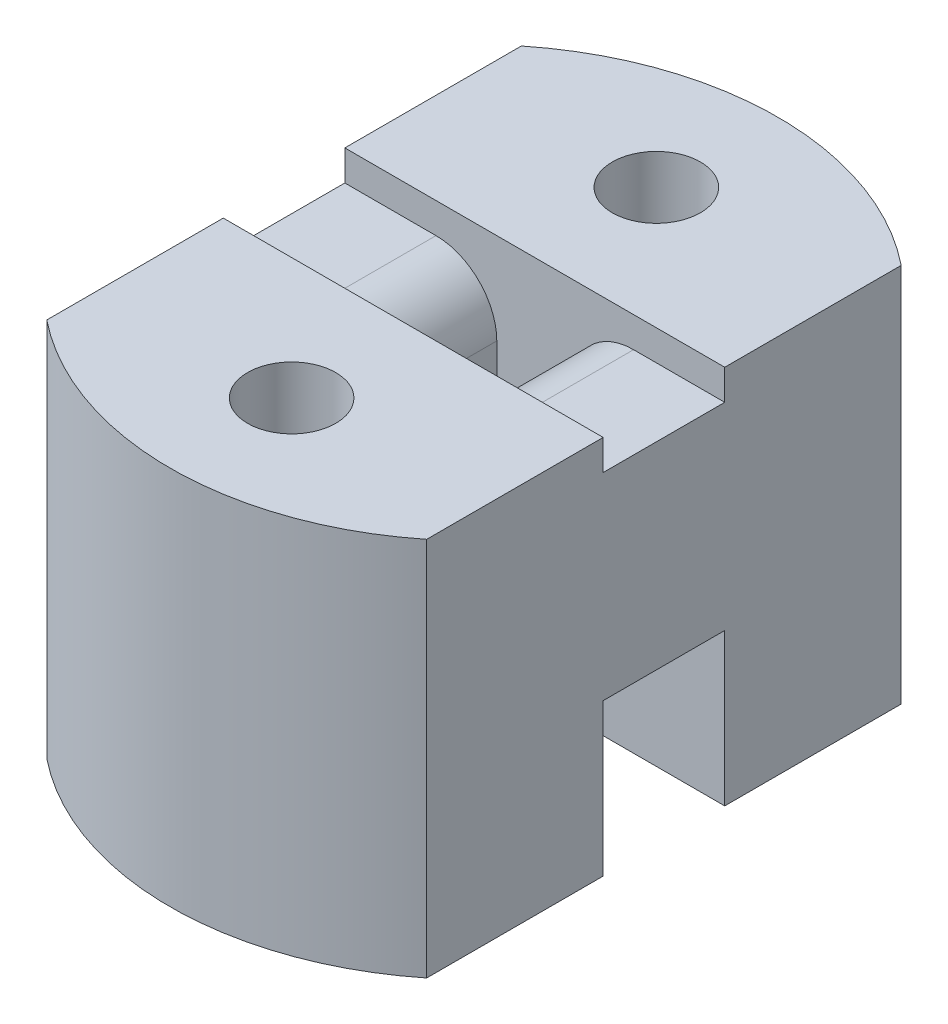
SolidWorks part; units mm, degrees
ref_plane "Front Plane" through (0, 0, 0) normal (0, 0, 1) x (1, 0, 0)
ref_plane "Top Plane" through (0, 0, 0) normal (0, 1, 0) x (1, 0, 0)
ref_plane "Right Plane" through (0, 0, 0) normal (1, 0, 0) x (0, 0, -1)
sketch "Sketch1" plane through (0, 0, 0) normal (0, 1, 0) x (1, 0, 0)
  circle A0 centre (0, 0) radius 20
  dimension "D1" = 40
extrude "Boss-Extrude1" add sketch "Sketch1" along normal blind 25
sketch "Sketch2" plane through (0, 25, 0) normal (0, 1, 0) x (1, 0, 0)
  line L0 (20, 0) -> (0, 0) construction
  line L1 (-20, 4) -> (20, 4)
  line L2 (-20, 4) -> (-20, -4)
  line L3 (-20, -4) -> (20, -4)
  line L4 (20, 4) -> (20, -4)
  circle A0 centre (0, 0) radius 20 construction
  dimension "D1" = 8
extrude "Cut-Extrude1" cut sketch "Sketch2" against normal blind 2
sketch "Sketch3" plane through (0, 25, 0) normal (0, 1, 0) x (1, 0, 0)
  line L0 (0, 0) -> (0, 12) construction
  line L3 (0, 0) -> (0, -12) construction
  dimension "D1" = 12
hole_wizard "M5 Clearance Hole1" positions "3DSketch1" profile "Sketch4" hole size "M5" standard "ANSI Metric" end condition through all
sketch3d "3DSketch1"
  point P0 (0, 25, -12)
  point P3 (0, 25, 12)
sketch "Sketch4" plane through (0, 25, -12) normal (1, 0, 0) x (0, 0, 1)
  line L0 (0, 0) -> (0, 25)
  line L1 (0, 25) -> (2.9, 25)
  line L2 (2.9, 25) -> (2.9, 0)
  line L5 (2.9, 0) -> (0, 0)
  line L11 (0, -6.35) -> (0, 107.95) construction
  dimension "Thru Hole Dia." = 5.8
  dimension "Thru Hole Depth" = 25
sketch "Sketch5" plane through (0, 0, 0) normal (0, -1, 0) x (1, 0, 0)
  line L1 (4.9075, 12) -> (2.4537, 16.25)
  line L2 (2.4537, 16.25) -> (-2.4537, 16.25)
  line L3 (-2.4537, 16.25) -> (-4.9075, 12)
  line L4 (-4.9075, 12) -> (-2.4537, 7.75)
  line L5 (-2.4537, 7.75) -> (2.4537, 7.75)
  line L6 (2.4537, 7.75) -> (4.9075, 12)
  line L7 (4.9075, -12) -> (2.4537, -7.75)
  line L8 (2.4537, -7.75) -> (-2.4537, -7.75)
  line L9 (-2.4537, -7.75) -> (-4.9075, -12)
  line L10 (-4.9075, -12) -> (-2.4537, -16.25)
  line L11 (-2.4537, -16.25) -> (2.4537, -16.25)
  line L12 (2.4537, -16.25) -> (4.9075, -12)
  circle A0 centre (0, 12) radius 4.25 construction
  circle A1 centre (0, -12) radius 4.25 construction
  dimension "D1" = 8.5
extrude "Cut-Extrude2" cut sketch "Sketch5" against normal blind 6
sketch "Sketch6" plane through (0, 23, 0) normal (0, 1, 0) x (1, 0, 0)
  line L0 (19.5959, 4) -> (-19.5959, 4) construction
  line L1 (-2.5, 4) -> (2.5, 4)
  line L2 (-2.5, 4) -> (-2.5, -4)
  line L3 (-2.5, -4) -> (2.5, -4)
  line L4 (2.5, 4) -> (2.5, -4)
  line L5 (-19.5959, -4) -> (19.5959, -4) construction
  point P8 (0, 4)
  dimension "D1" = 5
extrude "Cut-Extrude3" cut sketch "Sketch6" against normal through all both and the other way through all
sketch "Sketch7" plane through (0, 0, 0) normal (0, -1, 0) x (1, 0, 0)
  line L0 (-20, -4) -> (-20, 4) construction
  line L1 (20, -4) -> (20, 4) construction
  line L2 (-20, -4) -> (20, -4) construction
  line L3 (-20, 4) -> (20, 4) construction
  line L4 (-20, -4) -> (-20, 4)
  line L5 (20, -4) -> (20, 4)
  line L6 (-20, -4) -> (20, -4)
  line L7 (-20, 4) -> (20, 4)
extrude "Cut-Extrude4" cut sketch "Sketch7" against normal blind 10
fillet "Fillet1" radius 4 4 edges at (-2.5, 23, 0) (2.5, 23, 0) (-2.5, 10, 0) (2.5, 10, 0)
sketch "Sketch8" plane through (0, 25, 0) normal (0, 1, 0) x (1, 0, 0)
  line L0 (0, 0) -> (0, 20) construction
  line L1 (-12.5, 20) -> (12.5, 20)
  line L2 (-12.5, 20) -> (-12.5, -20)
  line L3 (-12.5, -20) -> (12.5, -20)
  line L4 (12.5, 20) -> (12.5, -20)
  arc A0 (19.5959, 4) -> (-19.5959, 4) centre (0, 0) ccw construction
  arc A1 (-19.5959, -4) -> (19.5959, -4) centre (0, 0) ccw construction
  dimension "D1" = 25
extrude "Cut-Extrude5" cut sketch "Sketch8" against normal through all flip side to cut
